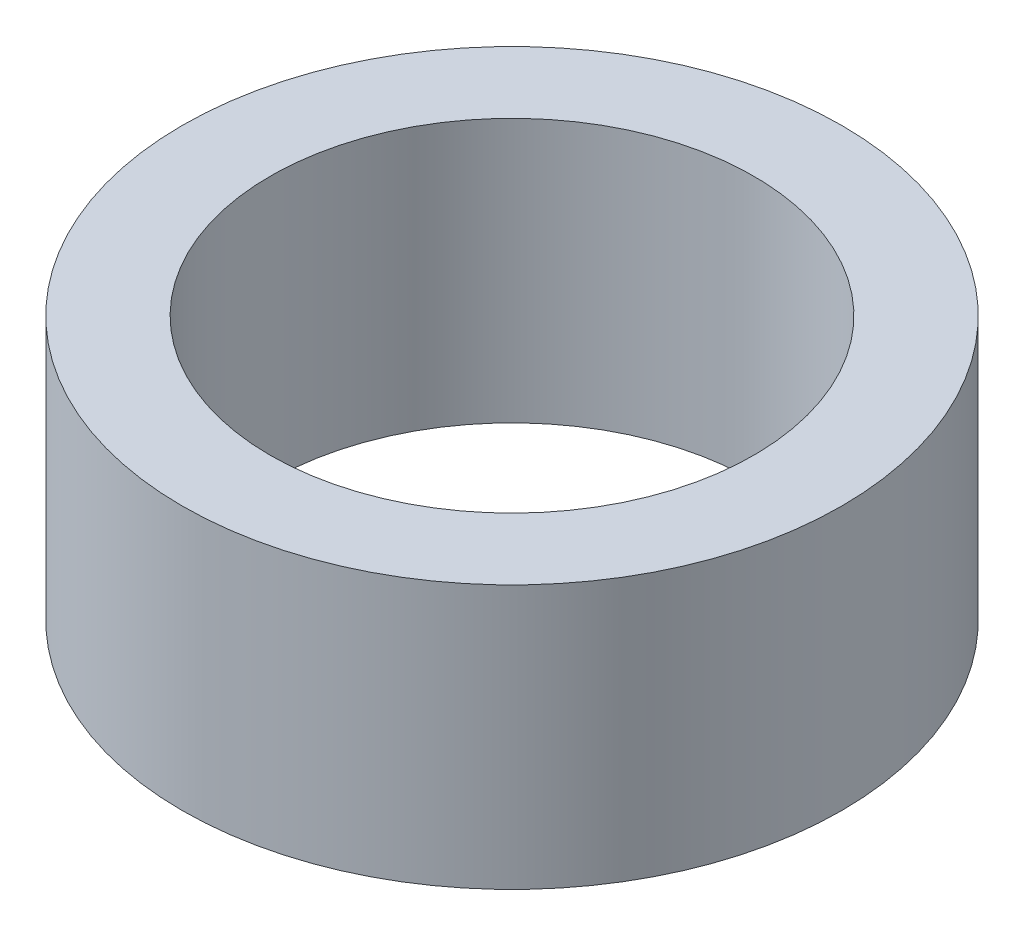
SolidWorks part; units mm, degrees
ref_plane "Front Plane" through (0, 0, 0) normal (0, 0, 1) x (1, 0, 0)
ref_plane "Top Plane" through (0, 0, 0) normal (0, 1, 0) x (1, 0, 0)
ref_plane "Right Plane" through (0, 0, 0) normal (1, 0, 0) x (0, 0, -1)
sketch "Sketch1" plane through (0, 0, 0) normal (0, 1, 0) x (1, 0, 0)
  circle A0 centre (0, 0) radius 37.5
  dimension "FLANGE_OD" = 75
extrude "Boss-Extrude1" add sketch "Sketch1" along normal blind 30
sketch "Sketch2" plane through (0, 0, 0) normal (0, 1, 0) x (1, 0, 0)
  circle A0 centre (0, 0) radius 27.5
  dimension "BORE_D" = 55
extrude "Cut-Extrude1" cut sketch "Sketch2" along normal through all
sketch "Sketch3" plane through (0, 30, 0) normal (0, 1, 0) x (1, 0, 0)
  circle A0 centre (0, 0) radius 16.5242 construction
  circle A1 centre (-16.5242, 0) radius 1.6636
  dimension "BOLT_D" = 3.3273
  dimension "BOLT_PCD" = 33.0485
extrude "Cut-Extrude2" cut sketch "Sketch3" against normal blind 19.0633 rebuild error yes
pattern_circular "CirPattern1" count 8 over 360 rebuild error yes
